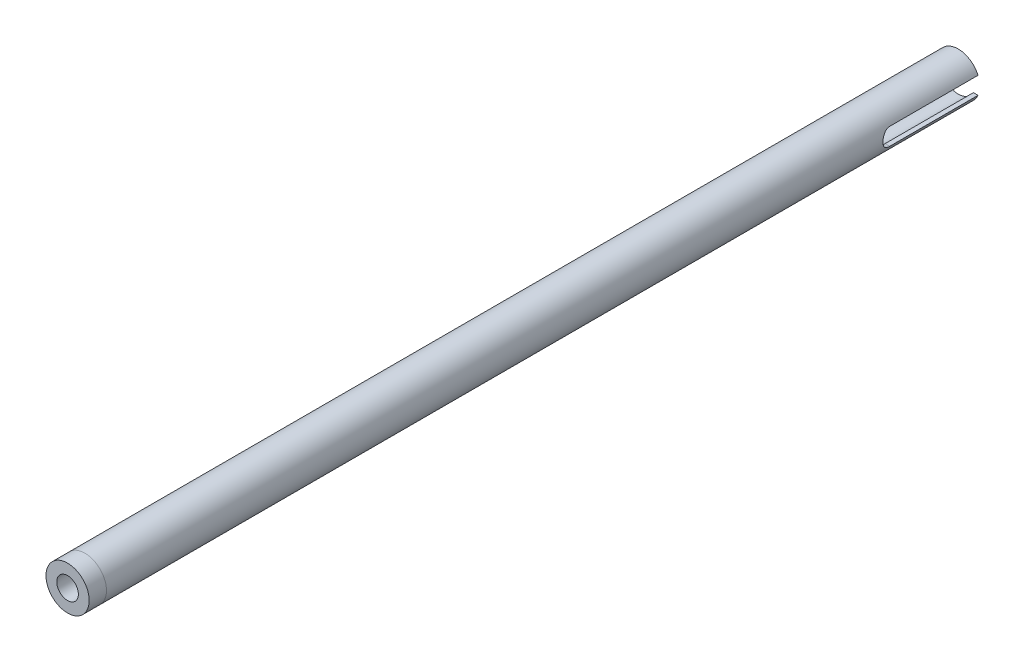
SolidWorks part; units mm, degrees
material "AISI 4130 Steel, annealed at 865C"
ref_plane "Front Plane" through (0, 0, 0) normal (0, 0, 1) x (1, 0, 0)
ref_plane "Top Plane" through (0, 0, 0) normal (0, 1, 0) x (1, 0, 0)
ref_plane "Right Plane" through (0, 0, 0) normal (1, 0, 0) x (0, 0, -1)
sketch "Axis" plane through (0, 0, 0) normal (0, 1, 0) x (1, 0, 0)
  line L0 (0, 0) -> (0, 326.9591) construction
  line L1 (0, 0) -> (0, -28.575) construction
  line L2 (0, 326.9591) -> (-7.9375, 326.9591) construction
  line L3 (0, 355.931) -> (-25.9803, 261.103) construction
  dimension "D1" = 28.575
  dimension "D2" = 7.9375
sketch "Sketch1" plane through (0, 0, 0) normal (0, 0, 1) x (1, 0, 0)
  line L0 (-7.9375, 0) -> (7.9375, 0) construction
  line L1 (-7.2748, 3.175) -> (7.2748, 3.175)
  line L2 (-7.2748, -3.175) -> (7.2748, -3.175)
  circle A0 centre (0, 0) radius 7.9375
  circle A1 centre (0, 0) radius 6.4135
  circle A2 centre (0, 0) radius 3.9688
  dimension "D1" = 15.875
  dimension "D3" = 7.9375
  dimension "D2" = 1.524
  dimension "D4" = 6.35
extrude "Threaded insert 1-1" add sketch "Sketch1" against normal blind 6.35 contours A2 L1 A1 | A1 L1 A0 | A2 L0 A1 L1 | A1 L0 A0 L1 | L0 A1 L2 A0 | L0 A2 L2 A1 | A2 L2 A1 | A1 L2 A0 | L0 A1 L2 A2 | L0 A0 L2 A1 | A0 L0 A1 L1 | A1 L0 A2 L1 region at (4.7887, 1.6543, 0) region at (4.7887, -1.6543, 0) region at (6.9234, 1.6163, 0) region at (6.9234, -1.6163, 0) region at (-4.7887, -1.6543, 0) region at (-4.7887, 1.6543, 0) region at (0, 4.6159, 0) region at (0, -4.6159, 0) region at (0, 6.5666, 0) region at (6.4237, -3.3281, 0) region at (-6.9234, -1.6163, 0) region at (-6.9234, 1.6163, 0)
extrude "Threaded insert 1-2" add sketch "Sketch1<3>" against normal blind 9.525 from surface contours A2 L1 A1 | A2 L0 A1 L1 | L0 A2 L2 A1 | A2 L2 A1 | L0 A1 L2 A2 | A1 L0 A2 L1 region at (4.7887, 1.6543, 0) region at (4.7887, -1.6543, 0) region at (-4.7887, -1.6543, 0) region at (-4.7887, 1.6543, 0) region at (0, 4.6159, 0) region at (0, -4.6159, 0) starting at face at (7.9375, 0, -6.35)
sketch "Sketch1<3>" plane through (0, 0, 0) normal (0, 0, 1) x (1, 0, 0) same geometry as "Sketch1"
extrude "A-arm tube" add sketch "Sketch1<4>" against normal up to vertex (326.9591 mm away) from surface separate body contours A1 L1 A0 | A1 L0 A0 L1 | L0 A1 L2 A0 | A1 L2 A0 | L0 A0 L2 A1 | A0 L0 A1 L1 region at (6.9234, 1.6163, 0) region at (6.9234, -1.6163, 0) region at (0, 6.5666, 0) region at (6.4237, -3.3281, 0) region at (-6.9234, -1.6163, 0) region at (-6.9234, 1.6163, 0) up to point (0, 0, -326.9591) starting at face at (6.4135, 0, -6.35)
sketch "Sketch1<4>" plane through (0, 0, 0) normal (0, 0, 1) x (1, 0, 0) same geometry as "Sketch1"
extrude "Apex slot" cut sketch "Sketch1<5>" along normal blind 35.56 from surface contours A0 L0 A1 L1 | L0 A0 L2 A1 | A1 L0 A0 L1 | L0 A1 L2 A0 region at (6.9234, 1.6163, 0) region at (6.9234, -1.6163, 0) region at (-6.9234, -1.6163, 0) region at (-6.9234, 1.6163, 0) starting at face at (6.4135, 0, -326.9591)
sketch "Sketch1<5>" plane through (0, 0, 0) normal (0, 0, 1) x (1, 0, 0) same geometry as "Sketch1"
fillet "Fillet1" radius 3.175 4 edges at (-6.4237, 3.175, -291.3991) (-6.4237, -3.175, -291.3991) (6.4237, -3.175, -291.3991) (6.4237, 3.175, -291.3991)
equation "\"tube diameter\"= 5 / 8"
equation "\"tube thickness\"= .06"
equation "\"apex thickness\"= .25"
equation "\"tube slot\"= 1.4"
equation "\"D1@Sketch1\"=\"tube diameter\""
equation "\"D2@Sketch1\"=\"tube thickness\""
equation "\"threaded insert hole\"= .3125"
equation "\"D3@Sketch1\"=\"threaded insert hole\""
equation "\"D4@Sketch1\"=\"apex thickness\""
equation "\"D1@Apex slot\" = \"tube slot\""
equation "\"D1@Fillet1\"=\"apex thickness\"/2"
